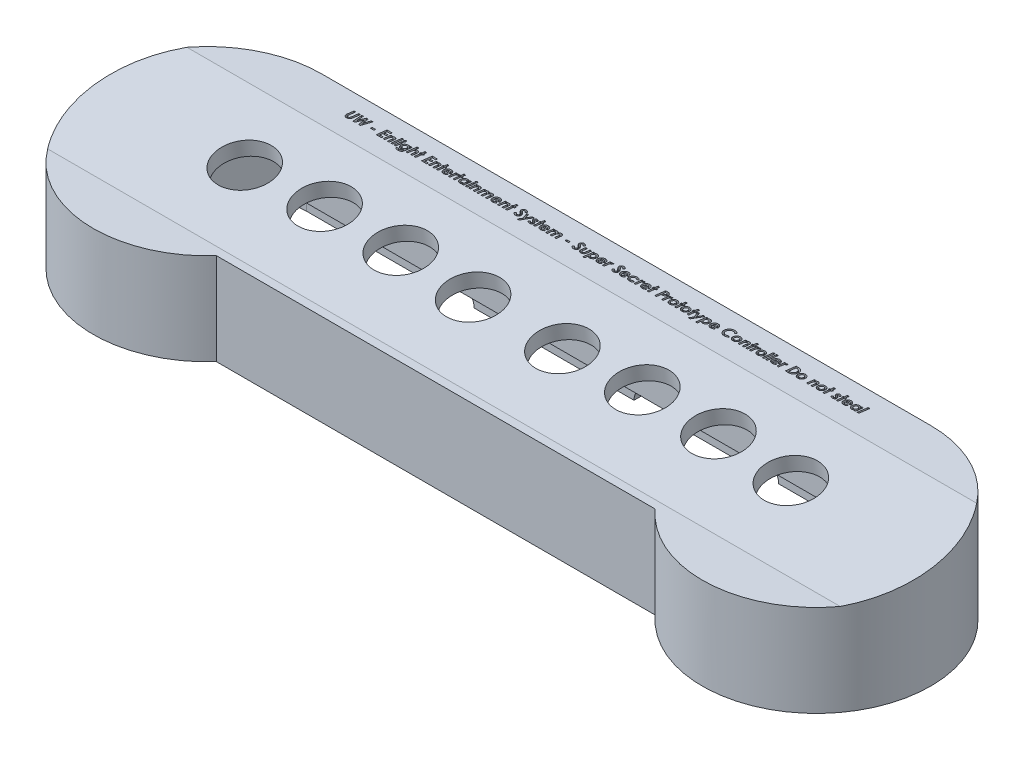
SolidWorks part; units mm, degrees
ref_plane "Front Plane" through (0, 0, 0) normal (0, 0, 1) x (1, 0, 0)
ref_plane "Top Plane" through (0, 0, 0) normal (0, 1, 0) x (1, 0, 0)
ref_plane "Right Plane" through (0, 0, 0) normal (1, 0, 0) x (0, 0, -1)
sketch "Sketch1" plane through (0, 0, 0) normal (0, 1, 0) x (1, 0, 0)
  line L3 (161.7, 30.2918) -> (-41.5, 30.2918)
  line L7 (-13.1019, -33.2082) -> (133.3019, -33.2082)
  line L8 (-63.3461, -39.0229) -> (-76.3578, -44.5347) construction
  line L9 (-41.5, -7.8082) -> (-79.6, -7.8082) construction
  line L10 (161.7, -7.8082) -> (199.8, -7.8082) construction
  arc A0 (-41.5, 30.2918) -> (-13.1019, -33.2082) centre (-41.5, -7.8082) ccw
  arc A1 (133.3019, -33.2082) -> (161.7, 30.2918) centre (161.7, -7.8082) ccw
  point P0 (0, 0)
  dimension "D4" = 76.2
  dimension "D2" = 203.2
  dimension "D1" = 38.1
  dimension "D3" = 63.5
extrude "Boss-Extrude1" add sketch "Sketch1" along normal blind 40.4
sketch "Sketch3" plane through (0, 0, 0) normal (1, 0, 0) x (0, 0, -1)
  line L2 (30.2918, 37.2179) -> (15.5, 37.2179)
  line L3 (30.2918, 40.4) -> (30.2918, 0) construction
  line L10 (55, 0) -> (-55, 0) construction
  line L14 (-30.5, 56.6478) -> (30.2918, 56.6478)
  line L15 (30.2918, 56.6478) -> (30.2918, 37.2179)
  line L18 (-56.0906, 56.6478) -> (-30.5, 56.6478)
  line L19 (15.5, 37.2179) -> (-30.5, 30.6308)
  line L20 (-30.5, 30.6308) -> (-56.0906, 30.6308)
  line L21 (-56.0906, 56.6478) -> (-56.0906, 30.6308)
  dimension "D1" = 37.2179
extrude "Cut-Extrude2" cut sketch "Sketch3" along normal through all both and the other way through all
sketch "Sketch2" plane through (0, 0, 0) normal (0, 1, 0) x (1, 0, 0)
  line L6 (161.7, 25.2918) -> (-41.5, 25.2918)
  line L7 (-15.4337, -28.2082) -> (135.6337, -28.2082)
  line L8 (161.7, 25.2918) -> (-41.5, 25.2918)
  line L9 (-15.4337, -28.2082) -> (135.6337, -28.2082)
  arc A8 (135.6337, -28.2082) -> (161.7, 25.2918) centre (161.7, -7.8082) ccw
  arc A9 (-41.5, 25.2918) -> (-15.4337, -28.2082) centre (-41.5, -7.8082) ccw
  arc A10 (135.6337, -28.2082) -> (161.7, 25.2918) centre (161.7, -7.8082) ccw
  arc A11 (-41.5, 25.2918) -> (-15.4337, -28.2082) centre (-41.5, -7.8082) ccw
  dimension "D1" = 5
extrude "Cut-Extrude3" cut sketch "Sketch2" along normal blind 5
sketch "Sketch4" plane through (0, 0, 0) normal (1, 0, 0) x (0, 0, -1)
  line L1 (22.6718, 32.1379) -> (15.5, 32.1379)
  line L4 (30.2918, 37.2179) -> (15.5, 37.2179) construction
  line L6 (22.6718, 5) -> (22.6718, 32.1379)
  line L7 (22.6718, 5) -> (-29.6351, 5)
  line L8 (15.5, 32.1379) -> (-29.6351, 25.5138)
  line L9 (15.5, 37.2179) -> (-30.5, 30.6308) construction
  line L11 (30.2918, 37.2179) -> (30.2918, 0) construction
  line L13 (-29.6351, 25.5138) -> (-29.6351, 5)
  dimension "D1" = 5.08
  dimension "D2" = 0.2
  dimension "D4" = 7.62
extrude "Cut-Extrude4" cut sketch "Sketch4" along normal blind 161.314 and the other way blind 41.32
sketch "Sketch5" plane through (0, 0, -30.2918) normal (0, 0, -1) x (-1, 0, 0)
  line L1 (41.91, 0) -> (-41.91, 0) construction
  line L5 (-161.7, 37.2179) -> (-161.7, 0) construction
  line L6 (41.5, 37.2179) -> (41.5, 0) construction
  circle A3 centre (-110.9, 0) radius 5.08
  circle A4 centre (-72.8, 0) radius 5.08
  circle A5 centre (-9.3, 0) radius 5.08
  point P10 (-161.7, 18.6089)
  dimension "D1" = 50.8
  dimension "D2" = 50.8
  dimension "D3" = 38.1
  dimension "D4" = 63.5
extrude "Cut-Extrude5" cut sketch "Sketch5" against normal blind 7.62
sketch "Sketch6" plane through (0, 37.2179, 0) normal (0, 1, 0) x (1, 0, 0)
  text T0 "<b><i>UW - Enlight Entertainment System - Super Secret Prototype Controller Do not steal</i></b>"
  dimension "D1" = 45.72
extrude "Cut-Extrude6" cut sketch "Sketch6" against normal blind 1.27
sketch "Sketch9" plane through (0, 34.2951, 4.911) normal (0, 0.9899, 0.1418) x (1, 0, 0)
  line L0 (191.8386, 20.6192) -> (-71.6386, 20.6192) construction
  circle A0 centre (125.7986, 0.2992) radius 8.9662
  circle A1 centre (151.1986, -0.9708) radius 8.9662
  circle A2 centre (74.9986, -0.9708) radius 8.9662
  circle A3 centre (100.3986, 0.2992) radius 8.9662
  circle A4 centre (-5.5986, 0.2992) radius 8.9662
  circle A5 centre (45.2014, -0.9708) radius 8.9662
  circle A6 centre (-30.9986, -0.9708) radius 8.9662
  circle A7 centre (19.8014, 0.2992) radius 8.9662
  dimension "D1" = 17.9324
  dimension "D10" = 17.9324
  dimension "D11" = 17.9324
  dimension "D12" = 17.9324
  dimension "D13" = 17.9324
  dimension "D14" = 17.9324
  dimension "D7" = 17.9324
  dimension "D15" = 17.9324
  dimension "D3" = 25.4
  dimension "D4" = 25.4
  dimension "D5" = 25.4
  dimension "D6" = 25.4
  dimension "D8" = 25.4
  dimension "D9" = 25.4
  dimension "D16" = 40.64
  dimension "D17" = 40.64
  dimension "D18" = 21.59
  dimension "D19" = 20.32
  dimension "D20" = 20.32
  dimension "D21" = 21.59
  dimension "D22" = 21.59
  dimension "D23" = 20.32
  dimension "D24" = 20.32
  dimension "D25" = 21.59
extrude "Cut-Extrude8" cut sketch "Sketch9" against normal blind 50.8
